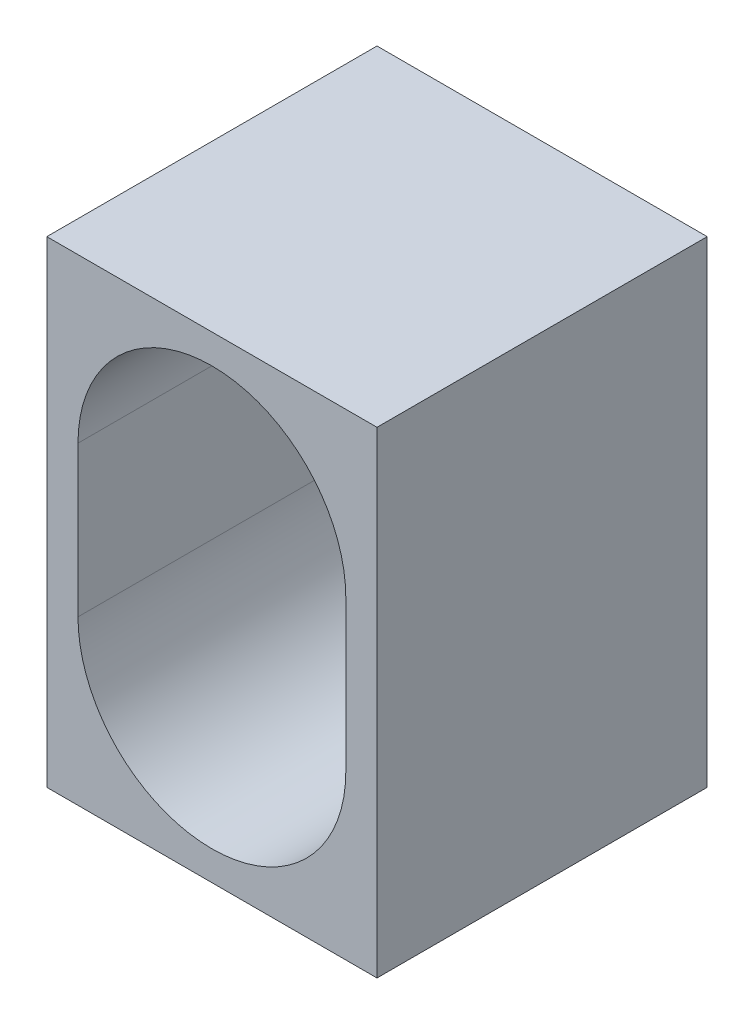
SolidWorks part; units mm, degrees
ref_plane "Front Plane" through (0, 0, 0) normal (0, 0, 1) x (1, 0, 0)
ref_plane "Top Plane" through (0, 0, 0) normal (0, 1, 0) x (1, 0, 0)
ref_plane "Right Plane" through (0, 0, 0) normal (1, 0, 0) x (0, 0, -1)
sketch "Sketch4" plane through (0, 0, 0) normal (0, 0, 1) x (1, 0, 0)
  line L1 (-30.2849, 20.5607) -> (14.7151, 20.5607)
  line L2 (-30.2849, 20.5607) -> (-30.2849, -44.4393)
  line L3 (-30.2849, -44.4393) -> (14.7151, -44.4393)
  line L4 (14.7151, 20.5607) -> (14.7151, -44.4393)
  dimension "D1" = 45
  dimension "D2" = 65
extrude "Boss-Extrude2" add sketch "Sketch4" along normal blind 45
sketch "Sketch5" plane through (0, 0, 45) normal (0, 0, 1) x (1, 0, 0)
  line L0 (-7.7849, -22.1893) -> (-7.7849, -1.6893) construction
  line L1 (-21.0349, -22.1893) -> (-21.0349, -1.6893) construction
  line L2 (5.4651, -22.1893) -> (5.4651, -1.6893) construction
  line L3 (-30.2849, -44.4393) -> (14.7151, -44.4393) construction
  line L4 (-30.2849, 20.5607) -> (-30.2849, -44.4393) construction
  line L5 (-26.0349, -22.1893) -> (-26.0349, -1.6893)
  line L6 (10.4651, -22.1893) -> (10.4651, -1.6893)
  arc A0 (-21.0349, -22.1893) -> (5.4651, -22.1893) centre (-7.7849, -22.1893) ccw construction
  arc A1 (5.4651, -1.6893) -> (-21.0349, -1.6893) centre (-7.7849, -1.6893) ccw construction
  arc A2 (10.4651, -1.6893) -> (-26.0349, -1.6893) centre (-7.7849, -1.6893) ccw
  arc A3 (-26.0349, -22.1893) -> (10.4651, -22.1893) centre (-7.7849, -22.1893) ccw
  point P2 (-7.7849, -11.9393)
  dimension "D3" = 5
  dimension "D1" = 32.5
  dimension "D2" = 22.5
extrude "Cut-Extrude1" cut sketch "Sketch5" against normal blind 42.5
